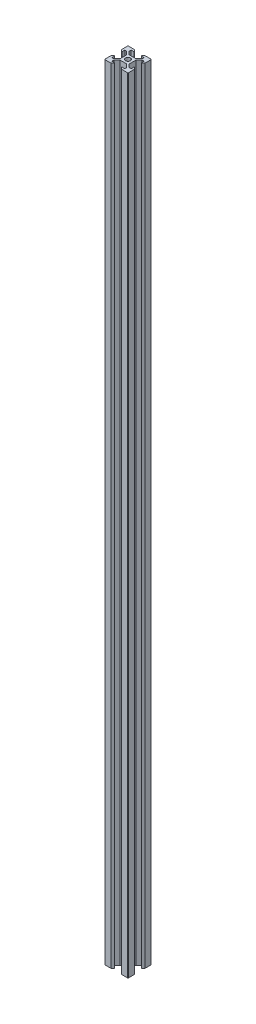
SolidWorks part; units mm, degrees
ref_plane "Front Plane" through (0, 0, 0) normal (0, 0, 1) x (1, 0, 0)
ref_plane "Top Plane" through (0, 0, 0) normal (0, 1, 0) x (1, 0, 0)
ref_plane "Right Plane" through (0, 0, 0) normal (1, 0, 0) x (0, 0, -1)
sketch "Sketch1" plane through (0, 0, 0) normal (0, 1, 0) x (1, 0, 0)
  line L0 (-2.1465, 12.2219) -> (22.938, 12.2219) construction
  line L1 (7.155, 13.9) -> (4.5, 16.555)
  line L2 (0.5, 0) -> (5.42, 0)
  line L3 (0, 0.5) -> (0, 5.42)
  line L4 (0.5, 20) -> (5.42, 20)
  line L5 (20, 0.5) -> (20, 19.5)
  line L6 (7.155, 13.9) -> (12.8341, 13.9)
  line L7 (6.1, 12.845) -> (6.1, 7.1491)
  line L8 (7.1445, 6.1) -> (12.8546, 6.1)
  line L9 (13.9, 12.8445) -> (13.9, 7.1491)
  line L10 (0, 20) -> (4.5, 20)
  line L11 (0, 20) -> (0, 15.5)
  line L12 (1.8, 15.5) -> (3.445, 15.5)
  line L13 (4.5, 18.2) -> (4.5, 16.555)
  line L14 (6.1, 12.845) -> (6.0943, 12.8393)
  line L15 (3.445, 15.5) -> (3.4393, 15.4943)
  line L16 (6.0943, 12.8393) -> (3.4393, 15.4943)
  line L17 (5.42, 20) -> (6.875, 18.545)
  line L18 (4.5, 20) -> (5.42, 20)
  line L19 (6.875, 20) -> (19.5, 20)
  line L20 (4.5, 18.2) -> (6.875, 18.2)
  line L21 (6.875, 20) -> (6.875, 18.2)
  line L22 (0, 14.58) -> (1.46, 13.12)
  line L23 (15.5, 18.2) -> (15.5, 16.555)
  line L24 (0, 15.5) -> (0, 13.12)
  line L25 (0, 13.12) -> (1.8, 13.12)
  line L26 (1.8, 15.5) -> (1.8, 13.12)
  line L27 (16.5507, 15.5) -> (18.2, 15.5)
  line L28 (15.5, 18.2) -> (13.12, 18.2)
  line L29 (13.12, 18.2) -> (13.12, 18.545)
  line L30 (13.12, 18.545) -> (14.575, 20)
  line L31 (18.2, 15.5) -> (18.2, 13.12)
  line L32 (18.2, 13.12) -> (18.5344, 13.12)
  line L33 (18.5344, 13.12) -> (20, 14.58)
  line L34 (12.8341, 13.9) -> (15.5, 16.555)
  line L35 (18.2, 4.5) -> (16.5585, 4.5)
  line L36 (16.5507, 15.5) -> (16.5585, 15.4922)
  line L37 (13.8926, 12.8372) -> (16.5585, 15.4922)
  line L38 (15.5, 3.4377) -> (15.5, 1.8)
  line L39 (18.2, 4.5) -> (18.2, 6.88)
  line L40 (18.2, 6.88) -> (18.6069, 6.88)
  line L41 (20, 5.42) -> (18.6069, 6.88)
  line L42 (15.5, 1.8) -> (13.12, 1.8)
  line L43 (13.12, 1.8) -> (13.12, 1.455)
  line L44 (14.575, 0) -> (13.12, 1.455)
  line L45 (13.9, 7.1491) -> (16.5585, 4.5)
  line L46 (12.8546, 6.1) -> (12.8412, 6.0865)
  line L47 (15.5, 3.4377) -> (15.4997, 3.4375)
  line L48 (12.8412, 6.0865) -> (15.4997, 3.4375)
  line L49 (1.8, 4.5) -> (3.4393, 4.5)
  line L50 (4.5, 3.4393) -> (4.5, 1.8)
  line L51 (1.46, 6.88) -> (1.8, 6.88)
  line L52 (1.8, 6.88) -> (1.8, 4.5)
  line L53 (0, 5.42) -> (1.46, 6.88)
  line L54 (4.5, 1.8) -> (6.875, 1.8)
  line L55 (6.875, 1.8) -> (6.875, 1.455)
  line L56 (5.42, 0) -> (6.875, 1.455)
  line L57 (3.4393, 4.5) -> (6.1, 7.1491)
  line L58 (14.575, 0) -> (19.5, 0)
  line L59 (7.1445, 6.1) -> (7.1583, 6.0861)
  line L60 (4.4977, 3.437) -> (7.1583, 6.0861)
  line L61 (0, 6.88) -> (0, 19.5)
  circle A0 centre (10, 10) radius 2.0746
  arc A1 (0.5, 0) -> (0, 0.5) centre (0.5, 0.5) cw
  arc A2 (19.5, 0) -> (20, 0.5) centre (19.5, 0.5) ccw
  arc A3 (19.5, 20) -> (20, 19.5) centre (19.5, 19.5) cw
  arc A4 (0, 19.5) -> (0.5, 20) centre (0.5, 19.5) cw
  point P22 (0, 0)
  point P25 (20, 0)
  dimension "D14" = 0.5
  dimension "D1" = 20
  dimension "D2" = 20
  dimension "D3" = 10
  dimension "D4" = 10
  dimension "D5" = 7.8
  dimension "D6" = 7.8
  dimension "D7" = 3.9
  dimension "D8" = 3.9
  dimension "D9" = 4.5
  dimension "D10" = 4.5
  dimension "D11" = 45
  dimension "D12" = 1.5
  dimension "D13" = 1.5
  dimension "D15" = 2.375
  dimension "D16" = 1.8
  dimension "D17" = 9.155
  dimension "D18" = 45
  dimension "D19" = 2.38
  dimension "D20" = 1.8
  dimension "D21" = 4.58
  dimension "D22" = 45
  dimension "D24" = 2.38
  dimension "D25" = 2.38
  dimension "D27" = 2.38
  dimension "D28" = 9.16
  dimension "D29" = 4.58
  dimension "D30" = 2.38
  dimension "D31" = 1.8
  dimension "D32" = 45
  dimension "D33" = 1.5
  dimension "D34" = 2.38
  dimension "D35" = 45
  dimension "D36" = 4.58
  dimension "D37" = 2.375
  dimension "D39" = 45
  dimension "D40" = 4.58
  dimension "D41" = 1.5
extrude "Boss-Extrude2" add sketch "Sketch1" along normal blind 1000 contours L7 L0 L9 L37 L36 L27 L31 L32 L33 L5 A3 L19 L30 L29 L28 L23 L34 L6 L1 L13 L20 L21 L17 L4 A4 L11 L24 L22 L25 L26 L12 L15 L16 L14 | L0 L7 L57 L49 L52 L51 L53 L3 A1 L2 L56 L55 L54 L50 L60 L59 L8 L46 L48 L47 L38 L42 L43 L44 L58 A2 L5 L41 L40 L39 L35 L45 L9 A0 region at (6.3146, 0, -12.5334) region at (10, 0, -12.1984)
ref_axis "Eje1" through (10, 666.9554, -10) along (0, -1, 0)
ref_plane "Plano1" through (0, 0, -10) normal (0, 0, -1) x (-1, 0, 0)
sketch "Croquis1" plane through (0, 1000, 0) normal (0, 1, 0) x (1, 0, 0)
  line L1 (20.9803, -1.3406) -> (-0.9803, -1.3406)
  line L2 (20.9803, -1.3406) -> (20.9803, 21.3406)
  line L3 (20.9803, 21.3406) -> (-0.9803, 21.3406)
  line L4 (-0.9803, -1.3406) -> (-0.9803, 21.3406)
  line L5 (20.9803, -1.3406) -> (-0.9803, 21.3406) construction
  line L6 (20.9803, 21.3406) -> (-0.9803, -1.3406) construction
  point P0 (10, 10)
extrude "Cortar-Extruir1" cut sketch "Croquis1" against normal blind 334
